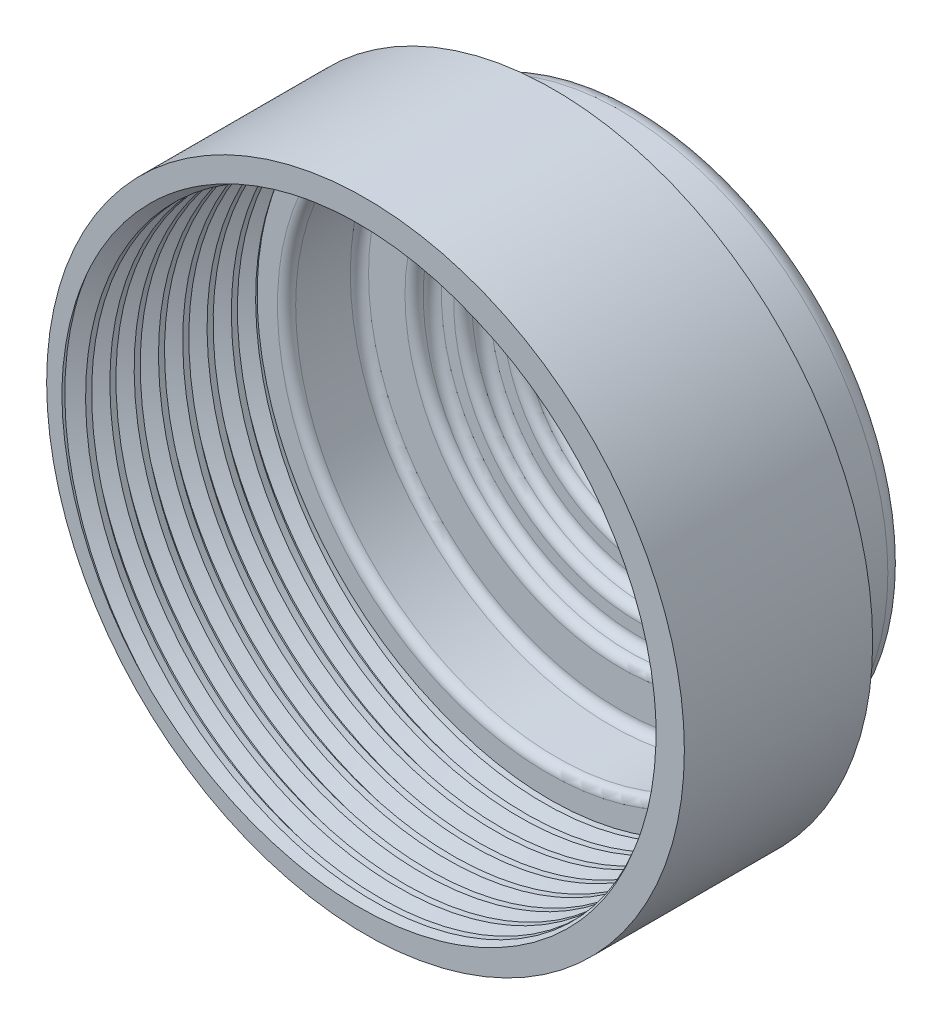
SolidWorks part; units mm, degrees
ref_plane "Plan de face" through (0, 0, 0) normal (0, 0, 1) x (1, 0, 0)
ref_plane "Plan de dessus" through (0, 0, 0) normal (0, 1, 0) x (1, 0, 0)
ref_plane "Plan de droite" through (0, 0, 0) normal (1, 0, 0) x (0, 0, -1)
sketch "Esquisse2" plane through (0, 0, 0) normal (0, 0, 1) x (1, 0, 0)
  circle A0 centre (-150, 595) radius 45 construction
  circle A1 centre (-150, 595) radius 45 construction
  circle A2 centre (-150, 595) radius 52.5
  circle A3 centre (-150, 595) radius 44
  circle A5 centre (-150, 595) radius 43
  circle A6 centre (-150, 595) radius 34
  circle A7 centre (-150, 595) radius 24
  circle A9 centre (-150, 595) radius 16.5
  circle A10 centre (-150, 595) radius 9
  circle A11 centre (-150, 595) radius 39
  circle A12 centre (-150, 595) radius 29
  circle A13 centre (-150, 595) radius 18.5
  circle A14 centre (-150, 595) radius 11
  circle M6 centre (-150, 595) radius 45
  dimension "D1" = 7.5
  dimension "D2" = 1
  dimension "D3" = 1
  dimension "D4" = 9
  dimension "D5" = 10
  dimension "D6" = 7.5
  dimension "D7" = 7.5
  dimension "D8" = 5
  dimension "D9" = 5
  dimension "D10" = 2
  dimension "D11" = 2
extrude "Boss.-Extru.1" add sketch "Esquisse2" along normal blind 1 contours A2 M6 | A3 M6 | A3 region at (-201.0151, 595, 0) region at (-193.8755, 595, 0) region at (-194.8727, 595, 0)
extrude "Boss.-Extru.2" add sketch "Esquisse2<3>" against normal blind 11 contours A3 A5 region at (-193.8755, 595, 0)
sketch "Esquisse2<3>" plane through (0, 0, 0) normal (0, 0, 1) x (1, 0, 0) same geometry as "Esquisse2"
extrude "Boss.-Extru.3" add sketch "Esquisse2<5>" against normal blind 3 from surface contours A3 | A6 starting at face at (-107, 595, -11)
sketch "Esquisse2<5>" plane through (0, 0, 0) normal (0, 0, 1) x (1, 0, 0) same geometry as "Esquisse2"
extrude "Boss.-Extru.4" add sketch "Esquisse2<6>" against normal blind 3 from surface contours A11 | A12 starting at face at (-116, 595, -14)
sketch "Esquisse2<6>" plane through (0, 0, 0) normal (0, 0, 1) x (1, 0, 0) same geometry as "Esquisse2"
extrude "Boss.-Extru.5" add sketch "Esquisse2<7>" against normal blind 3 from surface contours A6 | A7 starting at face at (-121, 595, -17)
sketch "Esquisse2<7>" plane through (0, 0, 0) normal (0, 0, 1) x (1, 0, 0) same geometry as "Esquisse2"
extrude "Boss.-Extru.6" add sketch "Esquisse2<8>" against normal blind 3 from surface contours A12 | A13 starting at face at (-126, 595, -20)
sketch "Esquisse2<8>" plane through (0, 0, 0) normal (0, 0, 1) x (1, 0, 0) same geometry as "Esquisse2"
extrude "Boss.-Extru.7" add sketch "Esquisse2<9>" against normal blind 3 from surface contours A7 | A9 starting at face at (-131.5, 595, -23)
sketch "Esquisse2<9>" plane through (0, 0, 0) normal (0, 0, 1) x (1, 0, 0) same geometry as "Esquisse2"
extrude "Boss.-Extru.8" add sketch "Esquisse2<10>" against normal blind 3 from surface separate body contours A13 starting at face at (-133.5, 595, -26)
sketch "Esquisse2<10>" plane through (0, 0, 0) normal (0, 0, 1) x (1, 0, 0) same geometry as "Esquisse2"
fillet "Congé1" radius 3 5 edges at (-126, 595, -26) (-121, 595, -23) (-116, 595, -20) (-111, 595, -17) (-106, 595, -14)
fillet "Congé2" radius 3 1 edges at (-131.5, 595, -29)
fillet "Congé3" radius 1.5 10 edges at (-133.5, 595, -23) (-131.5, 595, -20) (-126, 595, -17) (-121, 595, -14) (-116, 595, -11) (-107, 595, 1) (-126, 595, -20) (-121, 595, -17) (-116, 595, -14) (-107, 595, -11)
sketch "Esquisse3" plane through (0, 0, 1) normal (0, 0, 1) x (1, 0, 0)
  circle A0 centre (-150, 595) radius 52.5 construction
  circle A1 centre (-150, 595) radius 52.5
  circle A4 centre (-150, 595) radius 50
  dimension "D1" = 100
extrude "Boss.-Extru.9" add sketch "Esquisse3" along normal blind 30
thread "Filetage1" pitch 4 method extrude trim with start face yes trim with end face yes profile "Profil de filetage2" start angle 0, offset 3.5, length 33.5, pitch 4, diameter 100
ref_plane "Plan2" through (-200, 595, 34.5) normal (0, -1, 0) x (-1, 0, 0)
sketch "Profil de filetage2" plane through (-200, 595, 34.5) normal (0, -1, 0) x (-1, 0, 0)
  line L0 (0, 0) -> (0, 4) construction
  line L11 (0, 0) -> (0, 3.5)
  line L12 (0, 3.5) -> (-2.1651, 2.25)
  line L13 (-2.1651, 2.25) -> (-2.1651, 1.25)
  line L15 (-2.1651, 1.25) -> (0, 0)
  line L17 (-2.1651, 1.75) -> (0, 1.75) construction
  point P2 (0, 0)
  dimension "Pitch" = 4
  dimension "Profile_Angle" = 60
  dimension "Profile_Land" = 1
  dimension "Profile_Height" = 2.1651
